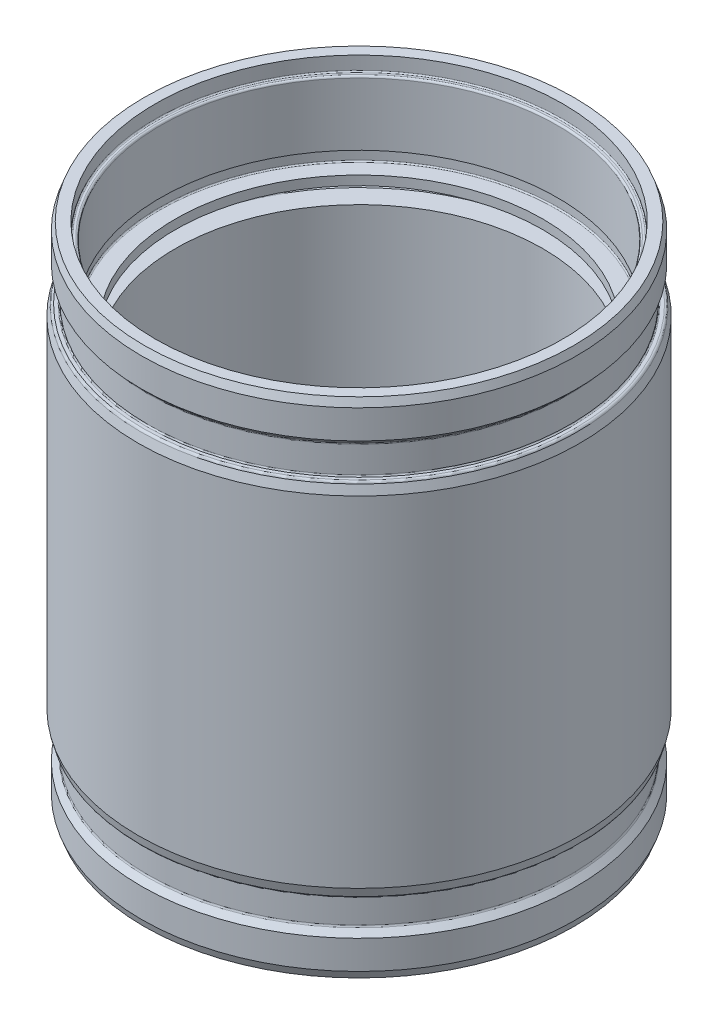
SolidWorks part; units mm, degrees
material "OVAKO 280 HB"
ref_plane "Front" through (0, 0, 0) normal (0, 0, 1) x (1, 0, 0)
ref_plane "Top" through (0, 0, 0) normal (0, 1, 0) x (1, 0, 0)
ref_plane "Right" through (0, 0, 0) normal (1, 0, 0) x (0, 0, -1)
sketch "Sketch1" plane through (0, 0, 0) normal (0, 0, 1) x (1, 0, 0)
  line L0 (62.5, 0) -> (69.6603, 0)
  line L1 (71, -5) -> (71, -9.65)
  line L2 (70.7, -9.95) -> (68.9, -9.95)
  line L3 (68.5, -10.35) -> (68.5, -13.35)
  line L4 (68.9, -13.75) -> (70.7, -13.75)
  line L5 (71, -14.05) -> (71, -19.4701)
  line L6 (70.7, -27.95) -> (68.9, -27.95)
  line L7 (68.5, -28.35) -> (68.5, -31.35)
  line L8 (68.9, -31.75) -> (70.7, -31.75)
  line L9 (71, -32.05) -> (71, -49.95)
  line L10 (71, -49.95) -> (70.2557, -52.7276)
  line L11 (69.966, -52.95) -> (68.8, -52.95)
  line L12 (68, -53.75) -> (68, -62.6436)
  line L13 (60.015, -75.7) -> (60.265, -75.95)
  line L14 (69.975, -64.95) -> (69.975, -67.1)
  line L15 (69.3668, -75.621) -> (69.975, -73.95)
  line L16 (69.725, -67.35) -> (67.9, -67.35)
  line L17 (68.897, -75.95) -> (60.265, -75.95)
  line L18 (60.015, -75.7) -> (60.015, -61.1916)
  line L19 (60.315, -44.95) -> (67.15, -44.95)
  line L20 (67.55, -44.55) -> (67.55, -39.05)
  line L21 (67.15, -38.65) -> (60.525, -38.65)
  line L22 (60.225, -38.35) -> (60.225, -35.4227)
  line L23 (60.2652, -35.2727) -> (61, -34)
  line L24 (61, -34) -> (61, -1.5)
  line L25 (0, 0) -> (0, -75.72) construction
  line L26 (71, -24.4299) -> (71, -27.65)
  line L27 (60.015, -59.7084) -> (60.015, -53.1916)
  line L28 (60.015, -51.7084) -> (60.015, -47.45)
  line L29 (67.5, -67.75) -> (67.5, -70.75)
  line L30 (67.9, -71.15) -> (69.725, -71.15)
  line L31 (69.975, -71.4) -> (69.975, -73.95)
  line L32 (69.975, -64.95) -> (68.2343, -63.2093)
  line L33 (62.5, 0) -> (61, -1.5)
  line L34 (69.6603, 0) -> (71, -5)
  line L35 (62.8749, -47.45) -> (62.8749, -75.95) construction
  line L36 (60.015, -47.45) -> (62.8749, -47.45) construction
  line L37 (60.015, -47.45) -> (60.015, -45.25)
  line L38 (62.8749, -71.85) -> (58.1091, -71.85) construction
  arc A0 (70.8393, -19.7358) -> (70.8393, -24.1642) centre (72, -21.95) ccw
  arc A1 (70.7, -9.95) -> (71, -9.65) centre (70.7, -9.65) ccw
  arc A2 (70.7, -13.75) -> (71, -14.05) centre (70.7, -14.05) cw
  arc A3 (70.8393, -19.7358) -> (71, -19.4701) centre (70.7, -19.4701) ccw
  arc A4 (71, -24.4299) -> (70.8393, -24.1642) centre (70.7, -24.4299) ccw
  arc A5 (70.7, -27.95) -> (71, -27.65) centre (70.7, -27.65) ccw
  arc A6 (71, -32.05) -> (70.7, -31.75) centre (70.7, -32.05) ccw
  arc A7 (69.975, -67.1) -> (69.725, -67.35) centre (69.725, -67.1) cw
  arc A8 (69.975, -71.4) -> (69.725, -71.15) centre (69.725, -71.4) ccw
  arc A9 (60.225, -35.4227) -> (60.2652, -35.2727) centre (60.525, -35.4227) cw
  arc A10 (60.525, -38.65) -> (60.225, -38.35) centre (60.525, -38.35) cw
  arc A11 (60.015, -45.25) -> (60.315, -44.95) centre (60.315, -45.25) cw
  arc A12 (69.966, -52.95) -> (70.2557, -52.7276) centre (69.966, -52.65) ccw
  arc A13 (68.9, -9.95) -> (68.5, -10.35) centre (68.9, -10.35) ccw
  arc A14 (68.897, -75.95) -> (69.3668, -75.621) centre (68.897, -75.45) ccw
  arc A15 (67.9, -67.35) -> (67.5, -67.75) centre (67.9, -67.75) ccw
  arc A16 (68.2343, -63.2093) -> (68, -62.6436) centre (68.8, -62.6436) cw
  arc A17 (60.015, -61.1916) -> (60.015, -59.7084) centre (59.715, -60.45) ccw
  arc A18 (60.015, -53.1916) -> (60.015, -51.7084) centre (59.715, -52.45) ccw
  arc A19 (67.9, -71.15) -> (67.5, -70.75) centre (67.9, -70.75) cw
  arc A20 (68.8, -52.95) -> (68, -53.75) centre (68.8, -53.75) ccw
  arc A21 (68.9, -13.75) -> (68.5, -13.35) centre (68.9, -13.35) cw
  arc A22 (68.5, -28.35) -> (68.9, -27.95) centre (68.9, -28.35) cw
  arc A23 (68.9, -31.75) -> (68.5, -31.35) centre (68.9, -31.35) cw
  arc A24 (67.55, -44.55) -> (67.15, -44.95) centre (67.15, -44.55) cw
  arc A25 (67.15, -38.65) -> (67.55, -39.05) centre (67.15, -39.05) cw
  point P39 (71, -24.2413)
  point P88 (69.975, -71.15)
  dimension "D7" = 5
  dimension "D27" = 0.3
  dimension "D28" = 1.6
  dimension "D29" = 1.6
  dimension "D32" = 121.03
  dimension "D33" = 0.5
  dimension "D37" = 0.4
  dimension "D39" = 0.4
  dimension "D40" = 0.4
  dimension "D47" = 0.8
  dimension "D48" = 0.25
  dimension "D51" = 0.8
  dimension "D1" = 75.95
  dimension "D2" = 122
  dimension "D3" = 142
  dimension "D4" = 120.03
  dimension "D5" = 120.45
  dimension "D6" = 137
  dimension "D8" = 2
  dimension "D9" = 139.95
  dimension "D10" = 6.3
  dimension "D11" = 34
  dimension "D12" = 30
  dimension "D13" = 31
  dimension "D14" = 20
  dimension "D15" = 11
  dimension "D16" = 23
  dimension "D17" = 136
  dimension "D18" = 135.1
  dimension "D19" = 3.8
  dimension "D20" = 3.8
  dimension "D21" = 48
  dimension "D22" = 66
  dimension "D23" = 54
  dimension "D24" = 144
  dimension "D25" = 3
  dimension "D26" = 15
  dimension "D30" = 15.5
  dimension "D31" = 23.5
  dimension "D34" = 3.8
  dimension "D35" = 8.6
  dimension "D36" = 135
  dimension "D38" = 45
  dimension "D41" = 45
  dimension "D42" = 0.25
  dimension "D43" = 5
  dimension "D44" = 15
  dimension "D45" = 1.5
  dimension "D46" = 45
  dimension "D49" = 2.5
  dimension "D50" = 4.1
revolve "Revolve1" add sketch "Sketch1" angle 360 about L25 region at (65.3769, -37.4731, 0)
sketch "Sketch11" plane through (0, 0, 0) normal (0, 0, 1) x (1, 0, 0)
  line L0 (61.25, 0) -> (70.75, 0)
  line L1 (71, -0.25) -> (71, -9.65)
  line L2 (70.7, -9.95) -> (69.3, -9.95)
  line L3 (68.5, -10.75) -> (68.5, -13.15)
  line L4 (69.3, -13.95) -> (70.7, -13.95)
  line L5 (71, -14.25) -> (71, -19.4701)
  line L6 (70.7, -27.95) -> (69.3, -27.95)
  line L7 (68.5, -28.75) -> (68.5, -31.15)
  line L8 (69.3, -31.95) -> (70.7, -31.95)
  line L9 (71, -32.25) -> (71, -49.95)
  line L10 (71, -49.95) -> (70.2557, -52.7276)
  line L11 (69.966, -52.95) -> (68.8, -52.95)
  line L12 (68, -53.75) -> (68, -61.5292)
  line L13 (60.015, -75.7) -> (60.265, -75.95)
  line L14 (69.975, -64.95) -> (69.975, -66.65)
  line L15 (69.3668, -75.621) -> (69.975, -73.95)
  line L16 (69.675, -66.95) -> (68.3, -66.95)
  line L17 (68.897, -75.95) -> (60.265, -75.95)
  line L18 (60.015, -75.7) -> (60.015, -62.6916)
  line L19 (60.315, -44.95) -> (66.95, -44.95)
  line L20 (67.75, -44.15) -> (67.75, -39.45)
  line L21 (66.95, -38.65) -> (60.4, -38.65)
  line L22 (60.1, -38.35) -> (60.1, -31.1392)
  line L23 (60.1402, -30.9892) -> (61, -29.5)
  line L24 (61, -29.5) -> (61, -0.25)
  line L25 (0, 0) -> (0, -75.72) construction
  line L26 (71, -24.4299) -> (71, -27.65)
  line L27 (60.015, -61.2084) -> (60.015, -54.6916)
  line L28 (60.015, -53.2084) -> (60.015, -45.25)
  line L29 (67.5, -67.75) -> (67.5, -70.15)
  line L30 (68.3, -70.95) -> (69.675, -70.95)
  line L31 (69.975, -71.25) -> (69.975, -73.95)
  line L32 (69.975, -64.95) -> (68, -61.5292)
  line L33 (61.25, 0) -> (61, -0.25)
  line L34 (70.75, 0) -> (71, -0.25)
  line L35 (59, -39.05) -> (66.75, -39.05)
  line L36 (59, 2) -> (72, 2)
  line L37 (59, 2) -> (59, -39.05)
  line L38 (59, -78) -> (72, -78)
  line L39 (72, 2) -> (72, -78)
  line L40 (66.75, -39.05) -> (66.75, -44.55)
  line L41 (66.75, -44.55) -> (59, -44.55)
  line L42 (59, -44.55) -> (59, -78)
  arc A0 (70.8393, -19.7358) -> (70.8393, -24.1642) centre (72, -21.95) ccw
  arc A1 (70.7, -9.95) -> (71, -9.65) centre (70.7, -9.65) ccw
  arc A2 (70.7, -13.95) -> (71, -14.25) centre (70.7, -14.25) cw
  arc A3 (70.8393, -19.7358) -> (71, -19.4701) centre (70.7, -19.4701) ccw
  arc A4 (71, -24.4299) -> (70.8393, -24.1642) centre (70.7, -24.4299) ccw
  arc A5 (70.7, -27.95) -> (71, -27.65) centre (70.7, -27.65) ccw
  arc A6 (71, -32.25) -> (70.7, -31.95) centre (70.7, -32.25) ccw
  arc A7 (69.975, -66.65) -> (69.675, -66.95) centre (69.675, -66.65) cw
  arc A8 (69.975, -71.25) -> (69.675, -70.95) centre (69.675, -71.25) ccw
  arc A9 (60.1, -31.1392) -> (60.1402, -30.9892) centre (60.4, -31.1392) cw
  arc A10 (60.4, -38.65) -> (60.1, -38.35) centre (60.4, -38.35) cw
  arc A11 (60.015, -45.25) -> (60.315, -44.95) centre (60.315, -45.25) cw
  arc A12 (69.966, -52.95) -> (70.2557, -52.7276) centre (69.966, -52.65) ccw
  arc A13 (69.3, -9.95) -> (68.5, -10.75) centre (69.3, -10.75) ccw
  arc A14 (68.897, -75.95) -> (69.3668, -75.621) centre (68.897, -75.45) ccw
  arc A15 (68.3, -66.95) -> (67.5, -67.75) centre (68.3, -67.75) ccw
  arc A17 (60.015, -62.6916) -> (60.015, -61.2084) centre (59.715, -61.95) ccw
  arc A18 (60.015, -54.6916) -> (60.015, -53.2084) centre (59.715, -53.95) ccw
  arc A19 (68.3, -70.95) -> (67.5, -70.15) centre (68.3, -70.15) cw
  arc A20 (68.8, -52.95) -> (68, -53.75) centre (68.8, -53.75) ccw
  arc A21 (69.3, -13.95) -> (68.5, -13.15) centre (69.3, -13.15) cw
  arc A22 (68.5, -28.75) -> (69.3, -27.95) centre (69.3, -28.75) cw
  arc A23 (69.3, -31.95) -> (68.5, -31.15) centre (69.3, -31.15) cw
  arc A24 (67.75, -44.15) -> (66.95, -44.95) centre (66.95, -44.15) cw
  arc A25 (66.95, -38.65) -> (67.75, -39.45) centre (66.95, -39.45) cw
  point P39 (71, -24.2413)
  point P88 (69.975, -70.95)
  dimension "D7" = 5
  dimension "D27" = 0.3
  dimension "D28" = 1.6
  dimension "D29" = 1.6
  dimension "D32" = 119.43
  dimension "D33" = 0.5
  dimension "D37" = 0.8
  dimension "D39" = 0.8
  dimension "D40" = 0.8
  dimension "D47" = 0.8
  dimension "D48" = 0.3
  dimension "D1" = 75.95
  dimension "D2" = 122
  dimension "D3" = 142
  dimension "D4" = 120.03
  dimension "D5" = 120.2
  dimension "D6" = 137
  dimension "D8" = 2
  dimension "D9" = 139.95
  dimension "D10" = 6.3
  dimension "D11" = 29.5
  dimension "D12" = 30
  dimension "D13" = 31
  dimension "D14" = 20
  dimension "D15" = 11
  dimension "D16" = 23
  dimension "D17" = 136
  dimension "D18" = 135.5
  dimension "D19" = 4
  dimension "D20" = 4
  dimension "D21" = 48
  dimension "D22" = 66
  dimension "D23" = 54
  dimension "D24" = 144
  dimension "D25" = 3
  dimension "D26" = 15
  dimension "D30" = 14
  dimension "D31" = 22
  dimension "D34" = 4
  dimension "D35" = 9
  dimension "D36" = 135
  dimension "D38" = 30
  dimension "D41" = 45
  dimension "D42" = 0.25
  dimension "D43" = 0.25
  dimension "D44" = 45
  dimension "D45" = 0.25
  dimension "D46" = 45
  dimension "D49" = 80
  dimension "D50" = 2
  dimension "D51" = 144
  dimension "D52" = 118
  dimension "D53" = 133.5
  dimension "D54" = 5.5
  dimension "D55" = 0.4
revolve "OP20" [suppressed] add sketch "Sketch11" angle 360 about L25
sketch "Sketch12" plane through (0, 0, 0) normal (0, 0, 1) x (1, 0, 0)
  line L0 (60.75, 0) -> (71.25, 0)
  line L1 (71, -0.25) -> (71, -9.65) construction
  line L2 (70.7, -9.95) -> (69.3, -9.95) construction
  line L3 (68.5, -10.75) -> (68.5, -13.15) construction
  line L4 (69.3, -13.95) -> (70.7, -13.95) construction
  line L5 (71, -14.25) -> (71, -19.4701) construction
  line L6 (70.7, -27.95) -> (69.3, -27.95) construction
  line L7 (68.5, -28.75) -> (68.5, -31.15) construction
  line L8 (69.3, -31.95) -> (70.7, -31.95) construction
  line L9 (71, -32.25) -> (71, -49.95) construction
  line L10 (71, -49.95) -> (70.2557, -52.7276) construction
  line L11 (69.966, -52.95) -> (68.8, -52.95) construction
  line L12 (68, -53.75) -> (68, -61.5292) construction
  line L13 (60.015, -75.7) -> (60.265, -75.95) construction
  line L14 (69.975, -64.95) -> (69.975, -66.65) construction
  line L15 (69.3668, -75.621) -> (69.975, -73.95) construction
  line L16 (69.675, -66.95) -> (68.3, -66.95) construction
  line L17 (69.6041, -75.95) -> (59.765, -75.95)
  line L18 (60.015, -75.7) -> (60.015, -62.6916) construction
  line L19 (60.315, -44.95) -> (66.95, -44.95) construction
  line L20 (67.75, -44.15) -> (67.75, -39.45) construction
  line L21 (66.95, -38.65) -> (60.4, -38.65) construction
  line L22 (60.1, -38.35) -> (60.1, -31.1392) construction
  line L23 (60.1402, -30.9892) -> (61, -29.5) construction
  line L24 (61, -29.5) -> (61, -0.25) construction
  line L25 (0, 0) -> (0, -75.72) construction
  line L26 (71, -24.4299) -> (71, -27.65) construction
  line L27 (60.015, -61.2084) -> (60.015, -54.6916) construction
  line L28 (60.015, -53.2084) -> (60.015, -45.25) construction
  line L29 (67.5, -67.75) -> (67.5, -70.15) construction
  line L30 (68.3, -70.95) -> (69.675, -70.95) construction
  line L31 (69.975, -71.25) -> (69.975, -73.95) construction
  line L32 (69.975, -64.95) -> (68, -61.5292) construction
  line L33 (61.25, 0) -> (61, -0.25) construction
  line L34 (70.75, 0) -> (71, -0.25) construction
  line L35 (60.5, -29.366) -> (60.5, -0.25)
  line L36 (59.515, -75.9071) -> (59.515, -62.1736) construction
  line L37 (68.897, -75.95) -> (60.265, -75.95) construction
  line L38 (59.765, -75.95) -> (59.515, -75.7)
  line L39 (71.5, -0.25) -> (71.5, -9.65)
  line L40 (70.7, -10.45) -> (69.3, -10.45)
  line L41 (69, -10.75) -> (69, -13.15)
  line L42 (69.3, -13.45) -> (70.7, -13.45)
  line L43 (71.5, -14.25) -> (71.5, -19.4701)
  line L44 (71.5, -24.4299) -> (71.5, -27.65)
  line L45 (70.7, -28.45) -> (69.3, -28.45)
  line L46 (69, -28.75) -> (69, -31.15)
  line L47 (69.3, -31.45) -> (70.7, -31.45)
  line L48 (71.5, -32.25) -> (71.5, -50.0158)
  line L49 (71.5, -50.0158) -> (70.7387, -52.8571)
  line L50 (69.966, -53.45) -> (68.8, -53.45)
  line L51 (68.5, -53.75) -> (68.5, -61.3952)
  line L52 (70.475, -64.816) -> (68.5, -61.3952)
  line L53 (70.475, -64.816) -> (70.475, -66.65)
  line L54 (69.675, -67.45) -> (68.3, -67.45)
  line L55 (68, -67.75) -> (68, -70.15)
  line L56 (68.3, -70.45) -> (69.675, -70.45)
  line L57 (70.475, -71.25) -> (70.475, -74.0382)
  line L58 (69.839, -75.7855) -> (70.475, -74.0382)
  line L59 (60.5, -29.366) -> (60.5, -0.0429) construction
  line L60 (61.25, 0) -> (70.75, 0) construction
  line L61 (59.515, -75.7) -> (59.515, -44.55)
  line L62 (69.8366, -75.792) -> (70.475, -74.0382) construction
  line L64 (60.5, -0.25) -> (60.75, 0)
  line L65 (71.5, -0.0429) -> (71.5, -9.65) construction
  line L66 (71.25, 0) -> (71.5, -0.25)
  line L67 (59.6, -39.05) -> (59.6, -31.1392)
  line L68 (59.7072, -30.7392) -> (60.5, -29.366)
  line L69 (61.0429, 0.5) -> (70.9571, 0.5) construction
  line L70 (61.0429, 0.5) -> (60.5, -0.0429) construction
  line L71 (70.9571, 0.5) -> (71.5, -0.0429) construction
  line L72 (68.897, -76.45) -> (60.0579, -76.45) construction
  line L73 (59.515, -75.9071) -> (60.0579, -76.45) construction
  line L74 (66.95, -39.15) -> (60.4, -39.15) construction
  line L75 (67.25, -44.15) -> (67.25, -39.45) construction
  line L76 (60.315, -44.45) -> (66.95, -44.45) construction
  line L77 (59.515, -53.7264) -> (59.515, -45.25) construction
  line L78 (59.6, -38.35) -> (59.6, -31.1392) construction
  line L80 (59.6, -39.05) -> (66.75, -39.05)
  line L81 (66.75, -39.05) -> (66.75, -44.55)
  line L82 (66.75, -44.55) -> (59.515, -44.55)
  line L83 (59.515, -61.7264) -> (59.515, -54.1736) construction
  arc A0 (70.8393, -19.7358) -> (70.8393, -24.1642) centre (72, -21.95) ccw construction
  arc A1 (70.7, -9.95) -> (71, -9.65) centre (70.7, -9.65) ccw construction
  arc A2 (70.7, -13.95) -> (71, -14.25) centre (70.7, -14.25) cw construction
  arc A3 (70.8393, -19.7358) -> (71, -19.4701) centre (70.7, -19.4701) ccw construction
  arc A4 (71, -24.4299) -> (70.8393, -24.1642) centre (70.7, -24.4299) ccw construction
  arc A5 (70.7, -27.95) -> (71, -27.65) centre (70.7, -27.65) ccw construction
  arc A6 (71, -32.25) -> (70.7, -31.95) centre (70.7, -32.25) ccw construction
  arc A7 (69.975, -66.65) -> (69.675, -66.95) centre (69.675, -66.65) cw construction
  arc A8 (69.975, -71.25) -> (69.675, -70.95) centre (69.675, -71.25) ccw construction
  arc A9 (60.1, -31.1392) -> (60.1402, -30.9892) centre (60.4, -31.1392) cw construction
  arc A10 (60.4, -38.65) -> (60.1, -38.35) centre (60.4, -38.35) cw construction
  arc A11 (60.015, -45.25) -> (60.315, -44.95) centre (60.315, -45.25) cw construction
  arc A12 (69.966, -52.95) -> (70.2557, -52.7276) centre (69.966, -52.65) ccw construction
  arc A13 (69.3, -9.95) -> (68.5, -10.75) centre (69.3, -10.75) ccw construction
  arc A14 (68.897, -75.95) -> (69.3668, -75.621) centre (68.897, -75.45) ccw construction
  arc A15 (68.3, -66.95) -> (67.5, -67.75) centre (68.3, -67.75) ccw construction
  arc A16 (70.7, -10.45) -> (71.5, -9.65) centre (70.7, -9.65) ccw
  arc A17 (60.015, -62.6916) -> (60.015, -61.2084) centre (59.715, -61.95) ccw construction
  arc A18 (60.015, -54.6916) -> (60.015, -53.2084) centre (59.715, -53.95) ccw construction
  arc A19 (68.3, -70.95) -> (67.5, -70.15) centre (68.3, -70.15) cw construction
  arc A20 (68.8, -52.95) -> (68, -53.75) centre (68.8, -53.75) ccw construction
  arc A21 (69.3, -13.95) -> (68.5, -13.15) centre (69.3, -13.15) cw construction
  arc A22 (68.5, -28.75) -> (69.3, -27.95) centre (69.3, -28.75) cw construction
  arc A23 (69.3, -31.95) -> (68.5, -31.15) centre (69.3, -31.15) cw construction
  arc A24 (67.75, -44.15) -> (66.95, -44.95) centre (66.95, -44.15) cw construction
  arc A25 (66.95, -38.65) -> (67.75, -39.45) centre (66.95, -39.45) cw construction
  arc A26 (69.3, -10.45) -> (69, -10.75) centre (69.3, -10.75) ccw
  arc A27 (69.3, -13.45) -> (69, -13.15) centre (69.3, -13.15) cw
  arc A28 (70.7, -13.45) -> (71.5, -14.25) centre (70.7, -14.25) cw
  arc A29 (71.0714, -20.1786) -> (71.5, -19.4701) centre (70.7, -19.4701) ccw
  arc A30 (71.0714, -20.1786) -> (71.0714, -23.7214) centre (72, -21.95) ccw
  arc A31 (71.5, -24.4299) -> (71.0714, -23.7214) centre (70.7, -24.4299) ccw
  arc A32 (70.7, -28.45) -> (71.5, -27.65) centre (70.7, -27.65) ccw
  arc A33 (69, -28.75) -> (69.3, -28.45) centre (69.3, -28.75) cw
  arc A34 (69.3, -31.45) -> (69, -31.15) centre (69.3, -31.15) cw
  arc A35 (71.5, -32.25) -> (70.7, -31.45) centre (70.7, -32.25) ccw
  arc A36 (69.966, -53.45) -> (70.7387, -52.8571) centre (69.966, -52.65) ccw
  arc A37 (68.8, -53.45) -> (68.5, -53.75) centre (68.8, -53.75) ccw
  arc A38 (70.475, -66.65) -> (69.675, -67.45) centre (69.675, -66.65) cw
  arc A39 (68.3, -67.45) -> (68, -67.75) centre (68.3, -67.75) ccw
  arc A40 (68.3, -70.45) -> (68, -70.15) centre (68.3, -70.15) cw
  arc A41 (70.475, -71.25) -> (69.675, -70.45) centre (69.675, -71.25) ccw
  arc A42 (69.839, -75.7855) -> (69.6041, -75.95) centre (69.6041, -75.7) cw
  arc A49 (59.6, -31.1392) -> (59.7072, -30.7392) centre (60.4, -31.1392) cw
  arc A50 (68.897, -76.45) -> (69.8366, -75.792) centre (68.897, -75.45) ccw construction
  arc A51 (60.4, -39.15) -> (59.6, -38.35) centre (60.4, -38.35) cw construction
  arc A52 (66.95, -39.15) -> (67.25, -39.45) centre (66.95, -39.45) cw construction
  arc A53 (67.25, -44.15) -> (66.95, -44.45) centre (66.95, -44.15) cw construction
  arc A54 (59.515, -45.25) -> (60.315, -44.45) centre (60.315, -45.25) cw construction
  arc A55 (59.515, -62.1736) -> (59.515, -61.7264) centre (59.715, -61.95) ccw construction
  arc A56 (59.515, -54.1736) -> (59.515, -53.7264) centre (59.715, -53.95) ccw construction
  point P39 (71, -24.2413)
  point P88 (69.975, -70.95)
  point P175 (59.515, -75.95)
  point P178 (60.5, 0)
  point P181 (71.5, 0)
  dimension "D7" = 5
  dimension "D27" = 0.3
  dimension "D28" = 1.6
  dimension "D29" = 1.6
  dimension "D32" = 119.43
  dimension "D33" = 0.5
  dimension "D37" = 0.8
  dimension "D39" = 0.8
  dimension "D40" = 0.8
  dimension "D47" = 0.8
  dimension "D48" = 0.3
  dimension "D59" = 0.25
  dimension "D1" = 75.95
  dimension "D2" = 61
  dimension "D3" = 71
  dimension "D4" = 60.015
  dimension "D5" = 60.1
  dimension "D6" = 68.5
  dimension "D8" = 2
  dimension "D9" = 69.975
  dimension "D10" = 6.3
  dimension "D11" = 29.5
  dimension "D12" = 30
  dimension "D13" = 31
  dimension "D14" = 20
  dimension "D15" = 11
  dimension "D16" = 23
  dimension "D17" = 68
  dimension "D18" = 67.75
  dimension "D19" = 4
  dimension "D20" = 4
  dimension "D21" = 48
  dimension "D22" = 66
  dimension "D23" = 54
  dimension "D24" = 144
  dimension "D25" = 3
  dimension "D26" = 15
  dimension "D30" = 14
  dimension "D31" = 22
  dimension "D34" = 4
  dimension "D35" = 9
  dimension "D36" = 67.5
  dimension "D38" = 30
  dimension "D41" = 45
  dimension "D42" = 0.25
  dimension "D43" = 0.25
  dimension "D44" = 45
  dimension "D45" = 0.25
  dimension "D46" = 45
  dimension "D50" = 0.25
  dimension "D51" = 45
  dimension "D52" = 0.25
  dimension "D53" = 45
  dimension "D54" = 0.25
  dimension "D55" = 45
  dimension "D56" = 0.4
  dimension "D57" = 5.5
  dimension "D58" = 133.5
  dimension "D49" = 0.5
revolve "OP40" [suppressed] add sketch "Sketch12" angle 360 about L25
sketch "Sketch3" plane through (0, 0, 0) normal (0, 0, 1) x (1, 0, 0)
  circle A0 centre (0, -21.95) radius 1.5
  dimension "D1" = 3
extrude "Cut-Extrude2" cut sketch "Sketch3" along normal through all
sketch "Sketch4" plane through (0, 0, 0) normal (1, 0, 0) x (0, 0, -1)
  line L0 (-61.0669, -45.25) -> (-68, -52.95) construction
  line L1 (-60.015, -45.25) -> (60.015, -45.25) construction
  line L2 (-68, -52.95) -> (68, -52.95) construction
  line L3 (-68, -52.95) -> (-85.2063, -52.95) construction
  dimension "D1" = 132
  dimension "D2" = 68
ref_plane "Plane1" through (0, -45.25, 61.0669) normal (0, -0.7431, 0.6691) x (1, 0, 0)
sketch "Sketch5" plane through (0, -45.25, 61.0669) normal (0, -0.7431, 0.6691) x (1, 0, 0)
  circle A0 centre (0, 0) radius 1.5
  dimension "D1" = 3
extrude "Cut-Extrude3" [suppressed] cut sketch "Sketch5" along normal blind 20 and the other way blind 10
ref_axis "Axis2" through (0, -34, 0) along (0, 1, 0)
pattern_circular "CirPattern1" [suppressed] count 2 over 360 about axis through (0, -34, 0) along (0, 1, 0)
sketch "Sketch6" plane through (0, 0, 0) normal (1, 0, 0) x (0, 0, -1)
  line L0 (-68, -61.95) -> (-60.015, -69.3961) construction
  line L1 (-68, -53.75) -> (-68, -62.6436) construction
  line L2 (-68.897, -75.95) -> (68.897, -75.95) construction
  line L4 (-68, -61.95) -> (-77.1298, -61.95) construction
  dimension "D1" = 137
  dimension "D2" = 60.015
  dimension "D3" = 14
  dimension "D4" = 6.5539
ref_plane "Plane2" through (0, -61.95, 68) normal (0, -0.682, -0.7314) x (-1, 0, 0)
sketch "Sketch7" plane through (0, -61.95, 68) normal (0, -0.682, -0.7314) x (-1, 0, 0)
  circle A0 centre (0, 0) radius 1.5
  dimension "D1" = 3
extrude "Cut-Extrude4" [suppressed] cut sketch "Sketch7" along normal blind 20 and the other way blind 20
pattern_circular "CirPattern2" [suppressed] count 2 over 360 about axis through (0, -34, 0) along (0, 1, 0)
sketch "Sketch8" plane through (0, 0, 0) normal (0, 0, 1) x (1, 0, 0)
  line L0 (0, 0) -> (0, 15.7928) construction
  line L1 (62.5, 0) -> (-62.5, 0) construction
  circle A0 centre (0, 4.5) radius 6
  dimension "D1" = 1.5
  dimension "D2" = 12
extrude "Extrude1" cut sketch "Sketch8" along normal through all and the other way through all
sketch "Sketch10" plane through (0, 0, 0) normal (1, 0, 0) x (0, 0, -1)
  line L0 (-39.8433, -60.4506) -> (47.3752, -60.4506) construction
  text T0 "7372 3475 00  1111- xx"
  line B0 (-28.4917, -61.2271) -> (-31.7602, -61.2271)
  line B1 (-28.9758, -60.5608) -> (-31.3813, -60.5608)
  line B2 (-31.7033, -61.1271) -> (-31.4381, -60.6608)
  line B3 (-30.5022, -57.7829) -> (-31.0722, -57.7829)
  line B4 (-31.7602, -55.5189) -> (-30.5022, -57.7829)
  line B5 (-28.9758, -60.5608) -> (-30.1603, -58.4136)
  line B6 (-27.5309, -58.4136) -> (-27.2321, -58.93)
  line B7 (-30.1561, -55.5189) -> (-31.7602, -55.5189)
  line B8 (-27.8748, -57.7829) -> (-27.5309, -58.4136)
  line B9 (-27.8748, -57.7829) -> (-28.7387, -56.3263)
  line B10 (-31.7602, -61.2271) -> (-34.2576, -61.2271)
  line B11 (-32.8535, -58.7579) -> (-34.2576, -61.2271)
  line B12 (-27.6766, -58.3132) -> (-27.9318, -57.8829)
  line B13 (-30.1561, -55.6189) -> (-31.5902, -55.6189)
  line B14 (-31.5902, -55.6189) -> (-30.3878, -57.7829)
  line B15 (-31.0722, -57.8829) -> (-27.9318, -57.8829)
  line B16 (-32.7679, -58.8096) -> (-34.0857, -61.1271)
  line B17 (-31.8183, -61.1271) -> (-34.0857, -61.1271)
  line B18 (-30.2183, -58.3132) -> (-27.6766, -58.3132)
  line B19 (-31.8183, -61.1271) -> (-30.2183, -58.3132)
  line B20 (-27.6464, -58.4136) -> (-27.3176, -58.982)
  line B21 (-28.4917, -61.1271) -> (-31.7033, -61.1271)
  line B22 (-30.3878, -57.7829) -> (-27.9911, -57.7829)
  line B23 (-27.9911, -57.7829) -> (-28.8247, -56.3773)
  line B24 (-28.8065, -60.6608) -> (-31.4381, -60.6608)
  line B25 (-28.8065, -60.6608) -> (-30.0461, -58.4136)
  line B26 (-30.0461, -58.4136) -> (-27.6464, -58.4136)
  line B27 (-31.3813, -60.5608) -> (-30.1603, -58.4136)
  arc B28 (-28.7387, -56.3263) -> (-30.1561, -55.5189) centre (-30.1561, -57.1669) ccw
  arc B29 (-28.4917, -61.2271) -> (-27.2321, -58.93) centre (-28.4917, -59.7332) ccw
  arc B30 (-31.0722, -57.7829) -> (-32.8535, -58.7579) centre (-31.0722, -59.8976) ccw
  arc B31 (-28.8247, -56.3773) -> (-30.1561, -55.6189) centre (-30.1561, -57.1669) ccw
  arc B32 (-31.0722, -57.8829) -> (-32.7679, -58.8096) centre (-31.0722, -59.8976) ccw
  arc B33 (-28.4917, -61.1271) -> (-27.3176, -58.982) centre (-28.4917, -59.7332) ccw
  dimension "D1" = 60.3
sketch_block_instance "SKETCH LOGO-1"
sketch_block "SKETCH LOGO" parameters "D1"=29.059, "D2"=11.4163, "D3"=29.624, "D4"=6.8884
wrap "Wrap1" [suppressed] sketch "Sketch10" source sketch "Sketch10" thickness 0.01 parameters "D1"=0.01
fillet "Fillet1" [suppressed] radius 1
sketch "Sketch15" [suppressed] plane through (0, 0, 0) normal (0, 0, 1) x (1, 0, 0)
  line L0 (0, 0) -> (0, -100.6082) construction
  line L1 (-68.897, -75.95) -> (68.897, -75.95) construction
  line L2 (60.1, -47.45) -> (64.5, -47.45)
  line L3 (57.4193, -41.7989) -> (57.4193, -75.95)
  line L4 (57.4193, -75.95) -> (66, -75.95)
  line L5 (64.3, -51.45) -> (64.3, -60.95)
  line L6 (60.1, -47.45) -> (60.1, -41.7989)
  line L7 (60.1, -41.7989) -> (57.4193, -41.7989)
  line L8 (64.9, -71.85) -> (65.6, -71.85)
  line L9 (66, -72.25) -> (66, -75.95)
  line L10 (64.3, -51.45) -> (64.9, -51.45)
  line L11 (64.9, -51.45) -> (64.9, -47.85)
  line L12 (62.8749, -71.85) -> (58.1091, -71.85) construction
  line L13 (64.3, -60.95) -> (65, -60.95) construction
  line L14 (65, -60.95) -> (65, -64.45) construction
  line L15 (65, -64.45) -> (64.3, -64.45) construction
  line L16 (64.3, -64.45) -> (64.3, -71.25)
  line L18 (64.3, -60.95) -> (64.3, -64.45)
  arc A0 (64.5, -47.45) -> (64.9, -47.85) centre (64.5, -47.85) cw
  arc A1 (65.6, -71.85) -> (66, -72.25) centre (65.6, -72.25) cw
  arc A2 (64.9, -71.85) -> (64.3, -71.25) centre (64.9, -71.25) cw
  dimension "D3" = 0.4
  dimension "D9" = 0.4
  dimension "D10" = 0.6
  dimension "D1" = 128.6
  dimension "D2" = 28.5
  dimension "D4" = 114.8387
  dimension "D5" = 120.2
  dimension "D6" = 5.6511
  dimension "D7" = 132
  dimension "D8" = 11.5
  dimension "D11" = 129.8
  dimension "D12" = 4
  dimension "D13" = 15
  dimension "D14" = 65
revolve "Cut-Revolve2" [suppressed] cut sketch "Sketch15" angle 360 about L0
sketch "Sketch13" plane through (0, 0, 0) normal (0, 0, 1) x (1, 0, 0)
  line L0 (0, 0) -> (0, -109.8751) construction
  line L1 (0, 0) -> (130.2141, 0) construction
  line L2 (59.5, -47.45) -> (59.5, -76.5)
  line L3 (59.5, 54.45) -> (66.25, 54.45)
  line L4 (59.5, -76.5) -> (69.579, -76.5)
  line L5 (71.5, 60.0158) -> (71.5, 0)
  line L6 (59.5, -47.45) -> (63.3, -47.45) construction
  line L7 (63.3, -47.45) -> (63.3, -76.5) construction
  line L8 (67.05, 53.65) -> (67.05, 49.95)
  line L9 (66.25, 49.15) -> (59.5, 49.15)
  line L10 (60.015, -47.45) -> (62.8749, -47.45) construction
  line L21 (60.315, -44.45) -> (67.05, -44.45)
  line L22 (67.05, -44.45) -> (67.05, -39.15)
  line L23 (67.05, -39.15) -> (60.525, -39.15)
  line L24 (59.5, -44.45) -> (66.25, -44.45)
  line L25 (67.05, -43.65) -> (67.05, -39.95)
  line L26 (66.25, -39.15) -> (59.5, -39.15)
  line L27 (69.975, -64.95) -> (68.2343, -63.2093) construction
  line L28 (71, -49.95) -> (70.2557, -52.7276) construction
  line L29 (68, -53.75) -> (68, -62.6436) construction
  line L30 (69.3668, -75.621) -> (69.975, -73.95) construction
  line L31 (69.975, -64.95) -> (69.975, -67.1) construction
  line L32 (69.966, -52.95) -> (68.8, -52.95) construction
  line L35 (71.5, -50.0158) -> (71.5, 0)
  line L36 (59.5, -44.45) -> (59.5, -47.45)
  line L37 (66.4395, 86.5) -> (66.4395, -76.5) construction
  line L38 (66.4395, 5) -> (-82.4958, 5) construction
  line L39 (71.5, 60.0158) -> (70.7387, 62.8571)
  line L40 (69.966, 63.45) -> (68.9, 63.45)
  line L41 (68.5, 63.85) -> (68.5, 72.4365)
  line L42 (68.7343, 73.0022) -> (70.475, 74.7429)
  line L43 (70.475, 74.7429) -> (70.475, 76.7)
  line L54 (70.475, -74.0382) -> (69.579, -76.5)
  line L55 (70.475, -66.7) -> (70.475, -74.0382)
  line L59 (70.475, -64.7429) -> (70.475, -66.7)
  line L60 (68.7343, -63.0022) -> (70.475, -64.7429)
  line L61 (68.5, -53.85) -> (68.5, -62.4365)
  line L62 (69.966, -53.45) -> (68.9, -53.45)
  line L63 (71.5, -50.0158) -> (70.7387, -52.8571)
  line L67 (70.475, 76.7) -> (70.475, 84.0382)
  line L68 (70.475, 84.0382) -> (69.579, 86.5)
  line L69 (59.5, 54.45) -> (59.5, 86.5)
  line L75 (59.5, 86.5) -> (69.579, 86.5)
  line L76 (59.5, 49.15) -> (59.5, -39.15)
  arc A0 (66.25, 54.45) -> (67.05, 53.65) centre (66.25, 53.65) cw
  arc A5 (67.05, 49.95) -> (66.25, 49.15) centre (66.25, 49.95) cw
  arc A6 (66.25, -44.45) -> (67.05, -43.65) centre (66.25, -43.65) ccw
  arc A7 (67.05, -39.95) -> (66.25, -39.15) centre (66.25, -39.95) ccw
  arc A10 (68.7343, -63.0022) -> (68.5, -62.4365) centre (69.3, -62.4365) cw
  arc A11 (68.5, 72.4365) -> (68.7343, 73.0022) centre (69.3, 72.4365) cw
  arc A13 (69.966, 63.45) -> (70.7387, 62.8571) centre (69.966, 62.65) cw
  arc A14 (68.9, 63.45) -> (68.5, 63.85) centre (68.9, 63.85) cw
  arc A29 (68.9, -53.45) -> (68.5, -53.85) centre (68.9, -53.85) ccw
  arc A30 (69.966, -53.45) -> (70.7387, -52.8571) centre (69.966, -52.65) ccw
  point P20 (66.4395, 5)
  point P57 (68.5, 72.7679)
  point P58 (68.5, -62.7679)
  dimension "D4" = 0.8
  dimension "D7" = 0.8
  dimension "D16" = 0.8
  dimension "D17" = 0.8
  dimension "D19" = 0.4
  dimension "D2" = 119
  dimension "D3" = 86.5
  dimension "D5" = 0.5
  dimension "D6" = 63.3
  dimension "D8" = 76.5
  dimension "D9" = 0.5
  dimension "D11" = 143
  dimension "D12" = 0.5
  dimension "D10" = 0.5
  dimension "D13" = 0.5
  dimension "D14" = 0.5
  dimension "D15" = 0.5
  dimension "D18" = 3.4342
revolve "Revolve2" add sketch "Sketch13" angle 360 about L0
sketch "Sketch14" plane through (0, 0, 0) normal (0, 0, 1) x (1, 0, 0)
  line L0 (0, 0) -> (0, -109.7083) construction
  line L1 (64.9, -71.85) -> (65.6, -71.85)
  line L2 (58.8156, -47.45) -> (64.5, -47.45)
  line L3 (58.8156, -47.45) -> (58.8156, -76.5)
  line L4 (58.8156, -76.5) -> (66, -76.5)
  line L5 (64.3, -51) -> (64.3, -60.95)
  line L6 (66, -72.25) -> (66, -76.5)
  line L7 (60.015, -47.45) -> (62.8749, -47.45) construction
  line L8 (59.5, -76.5) -> (69.579, -76.5) construction
  line L9 (-69.579, -76.5) -> (69.579, -76.5) construction
  line L10 (66.4395, 5) -> (106.6738, 5) construction
  line L11 (64.9, 61) -> (64.9, 57.85)
  line L12 (64.3, 61) -> (64.9, 61)
  line L13 (66, 82.25) -> (66, 86.5)
  line L14 (64.3, 61) -> (64.3, 70.95)
  line L15 (58.8156, 86.5) -> (66, 86.5)
  line L16 (58.8156, 57.45) -> (58.8156, 86.5)
  line L17 (64.3, -51) -> (64.9, -51)
  line L18 (64.9, -51) -> (64.9, -47.85)
  line L19 (58.8156, 57.45) -> (64.5, 57.45)
  line L20 (64.9, 81.85) -> (65.6, 81.85)
  line L21 (64.3, -60.95) -> (65, -60.95) construction
  line L22 (62.8749, -71.85) -> (58.1091, -71.85) construction
  line L23 (65, -60.95) -> (65, -64.5) construction
  line L24 (65, -64.5) -> (64.3, -64.5) construction
  line L25 (64.3, 74.5) -> (64.3, 70.95)
  line L28 (64.3, -64.5) -> (64.3, -71.25)
  line L29 (65, 74.5) -> (64.3, 74.5) construction
  line L30 (64.3, 70.95) -> (65, 70.95) construction
  line L31 (65, 70.95) -> (65, 74.5) construction
  line L32 (64.3, 74.5) -> (64.3, 81.25)
  line L33 (64.3, -60.95) -> (64.3, -64.5)
  arc A0 (64.5, -47.45) -> (64.9, -47.85) centre (64.5, -47.85) cw
  arc A1 (65.6, 81.85) -> (66, 82.25) centre (65.6, 82.25) ccw
  arc A2 (64.9, -71.85) -> (64.3, -71.25) centre (64.9, -71.25) cw
  arc A3 (65.6, -71.85) -> (66, -72.25) centre (65.6, -72.25) cw
  arc A4 (64.9, 81.85) -> (64.3, 81.25) centre (64.9, 81.25) ccw
  arc A5 (64.5, 57.45) -> (64.9, 57.85) centre (64.5, 57.85) ccw
  dimension "D3" = 0.4
  dimension "D6" = 0.6
  dimension "D7" = 0.4
  dimension "D1" = 128.6
  dimension "D2" = 117.6313
  dimension "D4" = 132
  dimension "D5" = 12
  dimension "D8" = 129.8
  dimension "D9" = 25.5
  dimension "D10" = 15.55
  dimension "D11" = 65
revolve "Cut-Revolve1" cut sketch "Sketch14" angle 360 about L0
